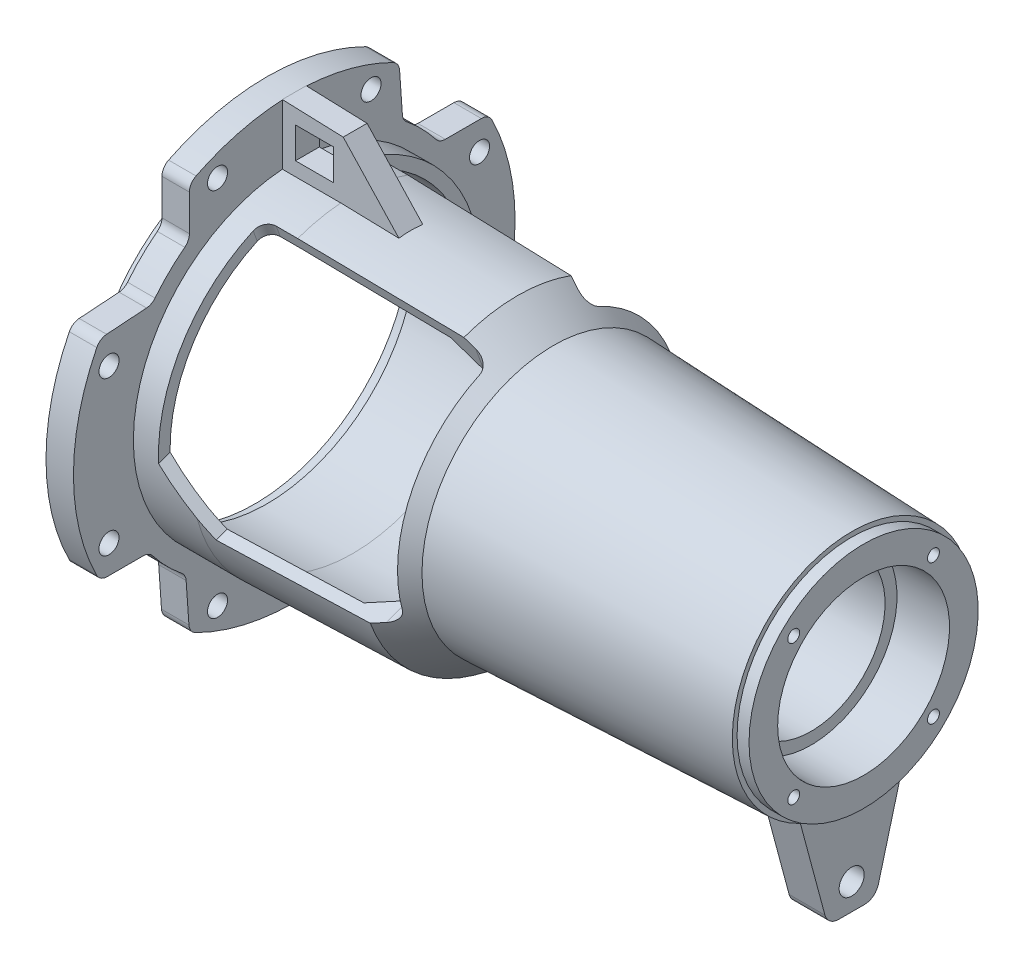
SolidWorks part; units mm, degrees
ref_plane "Front Plane" through (0, 0, 0) normal (0, 0, 1) x (1, 0, 0)
ref_plane "Top Plane" through (0, 0, 0) normal (0, 1, 0) x (1, 0, 0)
ref_plane "Right Plane" through (0, 0, 0) normal (1, 0, 0) x (0, 0, -1)
sketch "Sketch2" plane through (0, 0, 0) normal (0, 0, 1) x (1, 0, 0)
  line L0 (-127.5, 0) -> (127.5, 0) construction
  line L1 (13.5, 31) -> (105.5, 31)
  line L2 (105.5, 31) -> (105.5, 36)
  line L3 (105.5, 36) -> (127.5, 36)
  line L4 (127.5, 36) -> (127.5, 48)
  line L7 (122.5, 50) -> (-2.5, 55)
  line L8 (-2.5, 55) -> (-17.5, 65.6)
  line L9 (-17.5, 65.6) -> (-86.5, 67.4)
  line L11 (-111, 92.5) -> (-122.5, 92.5)
  line L12 (-122.5, 92.5) -> (-122.5, 70)
  line L13 (-122.5, 70) -> (-127.5, 70)
  line L17 (-8.5, 49.5) -> (-8.5, 36)
  line L18 (-8.5, 36) -> (13.5, 36)
  line L19 (13.5, 36) -> (13.5, 31)
  line L20 (-127.5, 70) -> (-127.5, 65)
  line L21 (-127.5, 65) -> (-122.5, 65)
  line L23 (-86.5, 67.4) -> (-111, 67.4)
  line L24 (-111, 67.4) -> (-111, 92.5)
  line L25 (-122.5, 65) -> (-122.5, 62.5)
  line L26 (-122.5, 62.5) -> (-86.5, 62.5)
  line L27 (127.5, 48) -> (122.5, 48)
  line L28 (122.5, 48) -> (122.5, 50)
  line L29 (-86.5, 62.5) -> (-24.6116, 60.8855)
  line L30 (-24.6116, 60.8855) -> (-8.5, 49.5)
  line L31 (-100.5, -7) -> (-80.5, -27)
  line L32 (-90.5, 53) -> (-18.5, 53)
  line L33 (-100.5, 43) -> (-100.5, -7)
  line L34 (-80.5, -27) -> (-18.5, -27)
  line L35 (-8.5, 43) -> (-8.5, -17)
  arc A0 (-18.5, -27) -> (-8.5, -17) centre (-18.5, -17) ccw
  arc A1 (-8.5, 43) -> (-18.5, 53) centre (-18.5, 43) ccw
  arc A2 (-90.5, 53) -> (-100.5, 43) centre (-90.5, 43) ccw
  point P4 (0, 0)
  point P25 (-100.5, -27)
  dimension "D24" = 10
  dimension "D1" = 255
  dimension "D2" = 62
  dimension "D3" = 72
  dimension "D4" = 5
  dimension "D5" = 110
  dimension "D6" = 96
  dimension "D7" = 125
  dimension "D8" = 99
  dimension "D9" = 131.2
  dimension "D10" = 185
  dimension "D11" = 125
  dimension "D12" = 130
  dimension "D13" = 140
  dimension "D14" = 100
  dimension "D15" = 110
  dimension "D16" = 5
  dimension "D17" = 11.5
  dimension "D18" = 41
  dimension "D19" = 92
  dimension "D20" = 27
  dimension "D21" = 134.8
  dimension "D22" = 22
  dimension "D23" = 22
  dimension "D25" = 20
  dimension "D26" = 45
  dimension "D27" = 80
  dimension "D28" = 53
revolve "Revolve1" add sketch "Sketch2" angle 360 about L0 region at (21.1624, 49.1925, 0)
sketch "Sketch4" plane through (0, 0, 0) normal (0, 0, 1) x (1, 0, 0)
  line L0 (-86.5, 67.4) -> (-111, 67.4) construction
  line L1 (-111, -92.5) -> (-111, 92.5) construction
  line L2 (-86.5, 67.4) -> (-111, 67.4)
  line L3 (-111, 67.4) -> (-111, 92.5)
  line L4 (-85.5, 91.6095) -> (-62.3364, 66.7696)
  line L5 (-111.3, 67.1) -> (-111, 67.4)
  line L6 (-111, 92.5) -> (-135.5403, 92.5) construction
  line L7 (-86.5039, 67.1) -> (-111.3, 67.1)
  line L8 (-17.5, 65.6) -> (-86.5, 67.4) construction
  line L9 (-62.3364, 66.7696) -> (-86.5, 67.4)
  line L10 (-111, 92.5) -> (-85.5, 91.6095)
  line L11 (-105.5, 86.0249) -> (-89.5, 86.0249)
  line L12 (-105.5, 86.0249) -> (-105.5, 73.0249)
  line L13 (-105.5, 73.0249) -> (-89.5, 73.0249)
  line L14 (-89.5, 86.0249) -> (-89.5, 73.0249)
  line L18 (-62.0496, 66.4621) -> (-86.5039, 67.1)
  line L19 (-111.3, 92.8107) -> (-85.3653, 91.905) construction
  line L20 (-85.3653, 91.905) -> (-61.6292, 66.4511) construction
  line L21 (-111.3, 67.1) -> (-111.3, 92.8107) construction
  line L22 (-62.3364, 66.7696) -> (-62.0496, 66.4621)
  line L23 (-61.6292, 66.4511) -> (-86.5039, 67.1) construction
  point P12 (-97.5, 86.0249)
  dimension "D1" = 2
  dimension "D2" = 45
  dimension "D3" = 25.5
  dimension "D4" = 16
  dimension "D5" = 13
  dimension "D6" = 6
  dimension "D7" = 5.5
  dimension "D8" = 0.3
extrude "Boss-Extrude5" add sketch "Sketch4" along normal mid plane 10 contours L22 L9 L2 L5 L7 L18 | L10 L3 L2 L9 L4 L11 L14 L13 L12 region at (-74.4195, 67.0356, 0) region at (-98.75, 67.9505, 0)
sketch "Sketch6" plane through (-122.5, 0, 0) normal (-1, 0, 0) x (0, 0, 1)
  line L0 (0, 0) -> (0, 121.8805) construction
  line L1 (0, 0) -> (42.9157, 103.6077) construction
  line L2 (0, 0) -> (-50.4459, 121.7871) construction
  line L3 (43.9275, 60.7896) -> (43.9275, 81.4041)
  line L4 (59.6615, 45.4478) -> (81.4041, 43.9275)
  line L5 (0, 0) -> (94.7185, 94.7185) construction
  line L6 (45.4478, -59.6615) -> (43.9275, -81.4041)
  line L7 (60.7896, -43.9275) -> (81.4041, -43.9275)
  line L8 (-59.6615, -45.4478) -> (-81.4041, -43.9275)
  line L9 (-43.9275, -60.7896) -> (-43.9275, -81.4041)
  line L10 (-45.4478, 59.6615) -> (-43.9275, 81.4041)
  line L11 (-60.7896, 43.9275) -> (-81.4041, 43.9275)
  circle A0 centre (0, 0) radius 84 construction
  circle A1 centre (32.1454, 77.6059) radius 4.2
  circle A2 centre (77.6059, 32.1454) radius 4.2
  circle A3 centre (77.6059, -32.1454) radius 4.2
  circle A4 centre (32.1454, -77.6059) radius 4.2
  circle A5 centre (-32.1454, -77.6059) radius 4.2
  circle A6 centre (-77.6059, -32.1454) radius 4.2
  circle A7 centre (-77.6059, 32.1454) radius 4.2
  circle A8 centre (-32.1454, 77.6059) radius 4.2
  circle A9 centre (0, 0) radius 92.5 construction
  arc A10 (81.4041, 43.9275) -> (43.9275, 81.4041) centre (0, 0) ccw
  arc A11 (59.6615, 45.4478) -> (43.9275, 60.7896) centre (0, 0) ccw
  arc A12 (43.9275, -81.4041) -> (81.4041, -43.9275) centre (0, 0) ccw
  arc A13 (45.4478, -59.6615) -> (60.7896, -43.9275) centre (0, 0) ccw
  arc A14 (-81.4041, -43.9275) -> (-43.9275, -81.4041) centre (0, 0) ccw
  arc A15 (-59.6615, -45.4478) -> (-43.9275, -60.7896) centre (0, 0) ccw
  arc A16 (-43.9275, 81.4041) -> (-81.4041, 43.9275) centre (0, 0) ccw
  arc A17 (-45.4478, 59.6615) -> (-60.7896, 43.9275) centre (0, 0) ccw
  point P24 (0, 0)
  point P31 (65.4074, 65.4074)
  point P47 (0, 0)
  dimension "D1" = 168
  dimension "D2" = 8.4
  dimension "D6" = 150
  dimension "D3" = 22.5
  dimension "D5" = 45
  dimension "D7" = 53
  dimension "D8" = 94
  dimension "D9" = 45
  dimension "D4" = 8
  dimension "D10" = 4
extrude "Cut-Extrude3" cut sketch "Sketch6" against normal up to next
fillet "Fillet1" radius 5 16 edges at (-116.75, 45.4478, 59.6615) (-116.75, -43.9275, 81.4041) (-116.75, -43.9275, 60.7896) (-116.75, -59.6615, 45.4478) (-116.75, -81.4041, 43.9275) (-116.75, -81.4041, -43.9275) (-116.75, -60.7896, -43.9275) (-116.75, -45.4478, -59.6615) (-116.75, -43.9275, -81.4041) (-116.75, 43.9275, -81.4041) (-116.75, 43.9275, -60.7896) (-116.75, 59.6615, -45.4478) (-116.75, 81.4041, -43.9275) (-116.75, 60.7896, 43.9275) (-116.75, 43.9275, 81.4041) (-116.75, 81.4041, 43.9275)
sketch "Sketch7" plane through (-127.5, 0, 0) normal (-1, 0, 0) x (0, 0, 1)
  line L0 (-16.93, 46.5148) -> (-23.0522, 63.3353)
  line L1 (-118.246, 0) -> (118.246, 0) construction
  line L2 (0, 78.393) -> (0, -78.393) construction
  line L3 (-46.5148, -16.93) -> (-63.3353, -23.0522)
  line L4 (46.5148, -16.93) -> (63.3353, -23.0522)
  line L5 (16.93, 46.5148) -> (23.0522, 63.3353)
  arc A0 (-5, 67.2143) -> (5, 67.2143) centre (0, 0) ccw construction
  arc A1 (0, -67.4) -> (0, 67.4) centre (0, 0) ccw construction
  circle A2 centre (0, 0) radius 49.5 construction
  arc A3 (0, -49.5) -> (0, 49.5) centre (0, 0) ccw construction
  arc A4 (-23.0522, 63.3353) -> (-63.3353, -23.0522) centre (0, 0) ccw
  arc A5 (-16.93, 46.5148) -> (-46.5148, -16.93) centre (0, 0) ccw
  circle A6 centre (0, 0) radius 65 construction
  arc A7 (16.93, 46.5148) -> (46.5148, -16.93) centre (0, 0) cw
  arc A8 (23.0522, 63.3353) -> (63.3353, -23.0522) centre (0, 0) cw
  point P11 (0, 0)
  point P13 (0, 0)
  dimension "D1" = 70
  dimension "D2" = 20
extrude "Cut-Extrude4" cut sketch "Sketch7" along normal offset from surface (92 mm away) 27 from surface up to face at (-127.5, 0, 65) starting at face at (-8.5, 0, 36)
chamfer "Chamfer1" distance 20 angle 45 2 edges at (-100.5, -22.2142, -61.033) (-100.5, -22.2142, 61.033)
fillet "Fillet2" radius 5 6 edges at (-8.5, -18.5956, 51.0911) (-8.5, 51.0911, 18.5956) (-100.5, 61.033, 22.2142) (-8.5, -18.5956, -51.0911) (-8.5, 51.0911, -18.5956) (-100.5, 61.033, -22.2142)
sketch "Sketch9" plane through (122.5, 0, 0) normal (1, 0, 0) x (0, 0, -1)
  line L0 (-21.4816, -45.1502) -> (-11.1916, -83.5529)
  line L1 (-5.396, -88) -> (5.396, -88)
  line L2 (11.1916, -83.5529) -> (21.4816, -45.1502)
  circle A0 centre (0, 0) radius 50 construction
  arc A1 (-21.4816, -45.1502) -> (21.4816, -45.1502) centre (0, 0) ccw
  arc A2 (11.1916, -83.5529) -> (5.396, -88) centre (5.396, -82) cw
  arc A3 (-5.396, -88) -> (-11.1916, -83.5529) centre (-5.396, -82) cw
  circle A4 centre (0, -77) radius 5.25
  point P2 (0, -50)
  point P7 (0, -88)
  point P10 (10, -88)
  point P13 (-10, -88)
  circle M5 centre (0, 0) radius 50
  dimension "D3" = 6
  dimension "D5" = 10.5
  dimension "D1" = 30
  dimension "D2" = 20
  dimension "D4" = 88
  dimension "D6" = 77
extrude "Boss-Extrude6" add sketch "Sketch9" against normal blind 15 contours A3 L1 A2 L2 L0 A4 M5 region at (122.5, -64.9147, 0)
hole_wizard "Tap Drill for M6x1.0 Tap1" positions "Sketch10" profile "Sketch11" hole size "M6x1.0" standard "ANSI Metric"
sketch "Sketch10" plane through (127.5, 0, 0) normal (1, 0, 0) x (0, 0, -1)
  line L0 (0, 0) -> (29.2669, 29.2669) construction
  line L3 (0, 0) -> (42, 0) construction
  circle A0 centre (0, 0) radius 42 construction
  point P0 (29.2669, 29.2669)
  point P19 (0, 25.3291)
  point P20 (29.2669, 29.2669)
  dimension "D1" = 84
  dimension "D2" = 45
sketch "Sketch11" plane through (127.5, 29.2669, -29.2669) normal (0, 1, 0) x (0, 0, -1)
  line L0 (0, 0) -> (0, 24)
  line L1 (0, 24) -> (2.5, 22.4978)
  line L2 (2.5, 22.4978) -> (2.5, 0)
  line L5 (2.5, 0) -> (0, 0)
  line L10 (0, 24) -> (-2.5, 22.4978) construction
  line L11 (0, -6.35) -> (0, 107.95) construction
  dimension "Hole Dia." = 5
  dimension "Hole Depth" = 24
  dimension "Drill Angle" = 118
pattern_circular "CirPattern1" count 4 over 360 about axis through (-127.5, 0, 0) along (-1, 0, 0) of "Tap Drill for M6x1.0 Tap1" reverse direction yes
hole_wizard "Tap Drill for M6x1.0 Tap2" positions "Sketch12" profile "Sketch13" hole size "M6x1.0" standard "ANSI Metric"
sketch "Sketch12" plane through (-8.5, 0, 0) normal (-1, 0, 0) x (0, 0, 1)
  line L0 (0, 0) -> (0, 119.8999) construction
  line L2 (0, 0) -> (29.6985, 29.6985) construction
  circle A0 centre (0, 0) radius 42 construction
  point P0 (29.6985, 29.6985)
  dimension "D1" = 84
  dimension "D2" = 45
sketch "Sketch13" plane through (-8.5, 29.6985, 29.6985) normal (0, 1, 0) x (0, 0, 1)
  line L0 (0, 0) -> (0, 24)
  line L1 (0, 24) -> (2.5, 22.4978)
  line L2 (2.5, 22.4978) -> (2.5, 0)
  line L5 (2.5, 0) -> (0, 0)
  line L10 (0, 24) -> (-2.5, 22.4978) construction
  line L11 (0, -6.35) -> (0, 107.95) construction
  dimension "Hole Dia." = 5
  dimension "Hole Depth" = 24
  dimension "Drill Angle" = 118
pattern_circular "CirPattern2" count 4 over 360 about axis through (122.5, 0, 0) along (1, 0, 0) of "Tap Drill for M6x1.0 Tap2"
